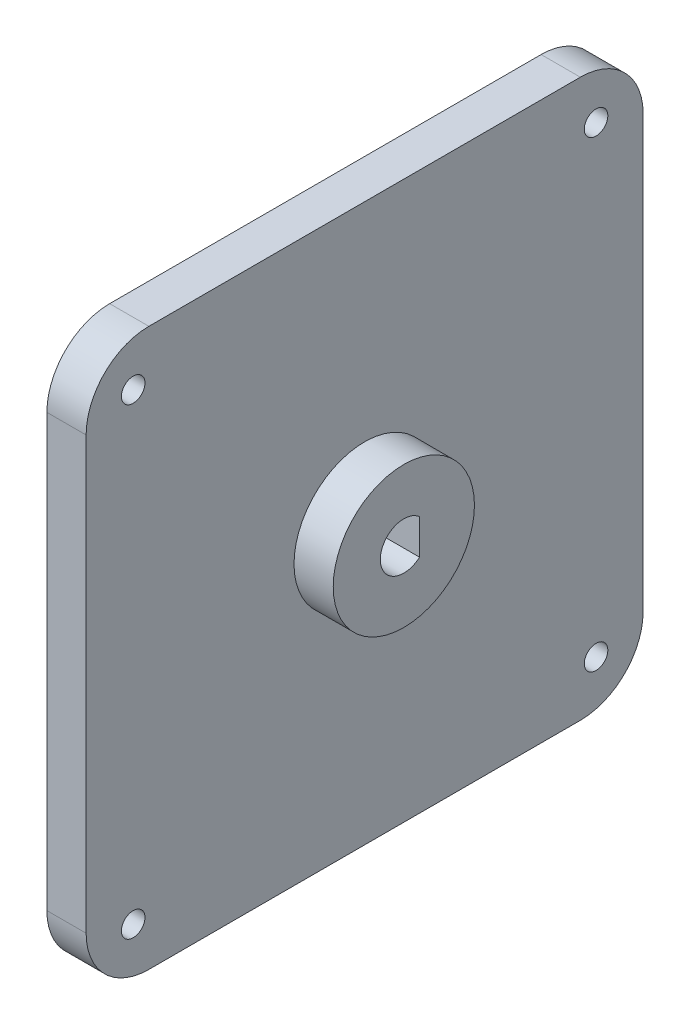
SolidWorks part; units mm, degrees
ref_plane "Front Plane" through (0, 0, 0) normal (0, 0, 1) x (1, 0, 0)
ref_plane "Top Plane" through (0, 0, 0) normal (0, 1, 0) x (1, 0, 0)
ref_plane "Right Plane" through (0, 0, 0) normal (1, 0, 0) x (0, 0, -1)
sketch "Sketch1" plane through (0, 0, 0) normal (1, 0, 0) x (0, 0, -1)
  line L1 (0, 0) -> (71, 0)
  line L2 (0, 0) -> (0, 71)
  line L3 (0, 71) -> (71, 71)
  line L4 (71, 0) -> (71, 71)
  circle A0 centre (6, 6) radius 1.5
  circle A1 centre (6, 65) radius 1.5
  circle A2 centre (65, 65) radius 1.5
  circle A3 centre (65, 6) radius 1.5
  dimension "D5" = 3
  dimension "D1" = 71
  dimension "D2" = 71
  dimension "D3" = 6
  dimension "D4" = 6
  dimension "D6" = 6
  dimension "D7" = 6
extrude "Boss-Extrude1" add sketch "Sketch1" along normal blind 5
fillet "Fillet1" radius 8 4 edges at (2.5, 0, 0) (2.5, 0, -71) (2.5, 71, -71) (2.5, 71, 0)
sketch "Sketch2" plane through (5, 0, 0) normal (1, 0, 0) x (0, 0, -1)
  line L1 (63, 71) -> (8, 71) construction
  line L2 (0, 63) -> (0, 8) construction
  circle A0 centre (35.5, 35.5) radius 9
  point P2 (35.5, 71)
  point P5 (0, 35.5)
  dimension "D1" = 18
  dimension "D2" = 35.5
  dimension "D3" = 35.5
extrude "Boss-Extrude2" add sketch "Sketch2" along normal blind 5
sketch "Sketch3" plane through (10, 0, 0) normal (1, 0, 0) x (0, 0, -1)
  line L1 (40.319, 39.6291) -> (37.5, 39.6291)
  line L2 (40.319, 39.6291) -> (40.319, 31.201)
  line L3 (40.319, 31.201) -> (37.5, 31.201)
  line L4 (37.5, 39.6291) -> (37.5, 31.201)
  circle A0 centre (35.5, 35.5) radius 3
  circle A1 centre (35.5, 35.5) radius 9 construction
  dimension "D1" = 6
  dimension "D2" = 2
extrude "Cut-Extrude1" cut sketch "Sketch3" against normal through all contours L4 A0 region at (10, 35.5, -35.204)
